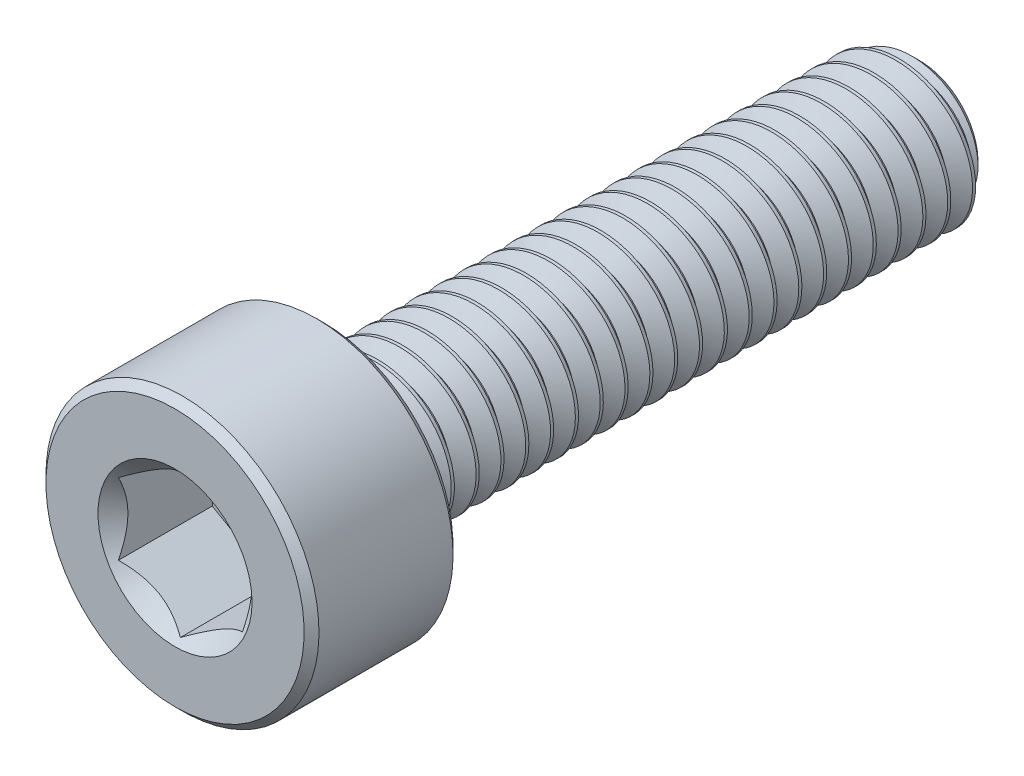
SolidWorks part; units mm, degrees
ref_plane "Front Plane" through (0, 0, 0) normal (0, 0, 1) x (1, 0, 0)
ref_plane "Top Plane" through (0, 0, 0) normal (0, 1, 0) x (1, 0, 0)
ref_plane "Right Plane" through (0, 0, 0) normal (1, 0, 0) x (0, 0, -1)
sketch "Sketch1" plane through (0, 0, 0) normal (1, 0, 0) x (0, 0, -1)
  line L0 (-7.5, 0) -> (7.5, 0) construction
  line L1 (7.5, 0) -> (7.5, 1.1752) construction
  line L2 (7.5, 1.1752) -> (7.1752, 1.5) construction
  line L3 (7.1752, 1.5) -> (7.125, 1.5) construction
  line L4 (7.125, 1.5) -> (-4.5, 1.5) construction
  line L5 (-4.5, 1.5) -> (-4.5, 2.75) construction
  line L6 (-4.5, 2.75) -> (-7.5, 2.75) construction
  line L7 (-7.5, 2.75) -> (-7.5, 0) construction
  line L8 (7.5, 1.1752) -> (7.5, 1.5) construction
  line L9 (7.4688, 1.5541) -> (7.7188, 1.1211) construction
  line L10 (7.7188, 1.1211) -> (7.9688, 1.5541) construction
  line L11 (7.9688, 1.5541) -> (7.4688, 1.5541) construction
  line L12 (7.7188, 1.5541) -> (7.7188, 1.5) construction
  line L13 (7.7188, 1.1211) -> (7.7188, 1.1752) construction
  line L14 (7.6875, 1.1752) -> (7.75, 1.1752) construction
  line L15 (7.5, 1.5) -> (7.9375, 1.5) construction
  line L16 (7.4844, 1.5271) -> (7.9531, 1.5271) construction
  line L17 (7.5, 0) -> (7.5, -1.5) construction
  line L18 (-4.65, 2.75) -> (-4.5, 2.6) construction
  line L19 (-7.35, 2.75) -> (-7.5, 2.6) construction
  line L20 (-4.5, 1.5) -> (-4.5, 0) construction
  line L21 (-4.5, 0.75) -> (-0.5, 0.75) construction
  line L22 (-0.5, 0.75) -> (3.5, 0.75) construction
  line L23 (3.5, 0.75) -> (7.5, 0.75) construction
  line L24 (-0.5, 0.75) -> (-0.5, 1.5) construction
  line L25 (-0.5, 1.5) -> (-0.5, 2.75) construction
  line L26 (3.5, 0.75) -> (3.5, 2.75) construction
  point P0 (-7.5, 1.25)
  point P3 (6.25, 1.5)
  point P4 (0, 0)
  point P18 (3.5, 1.5)
  point P22 (7.7188, 1.1752)
  point P24 (7.125, 1.5)
  point P25 (7.7188, 1.5)
  point P28 (7.7188, 1.5271)
  point P29 (6.25, -1.5)
  point P30 (-0.5, 1.5)
  point P31 (-6, 2.75)
  point P37 (-5.025, 2.75)
  point P38 (-7.275, 2.75)
  point P45 (-0.5, 0.75)
  point P46 (3.5, 0.75)
  dimension "D2" = 0.0625
  dimension "D7" = 0.15
  dimension "D8" = 0.15
  dimension "D9" = 0.15
  dimension "D10" = 0.075
  dimension "D11" = 0.375
  dimension "Drive Size" = 2.5
  dimension "Head Diameter" = 5.5
  dimension "Head Height" = 3
  dimension "Thread Pitch" = 0.5
  dimension "Thread Dia" = 3
  dimension "Length" = 12
  dimension "D12" = 0.375
  dimension "D4" = 1.25
  dimension "D3" = 45
sketch "Sketch2" plane through (0, 0, 0) normal (1, 0, 0) x (0, 0, -1)
  line L0 (-7.5, 0) -> (-7.5, 2.6)
  line L1 (-7.35, 2.75) -> (-4.65, 2.75)
  line L2 (-4.5, 2.6) -> (-4.5, 1.65)
  line L4 (7.1752, 1.5) -> (7.5, 1.1752)
  line L5 (7.5, 1.1752) -> (7.5, 0)
  line L6 (-4.5, 2.75) -> (-7.5, 2.75) construction
  line L7 (7.5, 0) -> (-7.5, 0)
  line L8 (-7.35, 2.75) -> (-7.5, 2.6) construction
  line L10 (-7.35, 2.75) -> (-7.5, 2.6)
  line L14 (-4.65, 2.75) -> (-4.5, 2.6) construction
  line L16 (-4.65, 2.75) -> (-4.5, 2.6)
  line L17 (-4.5, 1.5) -> (-4.5, 2.75) construction
  line L19 (-4.35, 1.5) -> (7.1752, 1.5)
  line L20 (7.125, 1.5) -> (-4.5, 1.5) construction
  arc A1 (-4.5, 1.65) -> (-4.35, 1.5) centre (-4.35, 1.65) ccw
  dimension "D3" = 0.15
revolve "Revolve1" add sketch "Sketch2" angle 360 about L7
sketch "Sketch3" plane through (0, 0, 7.5) normal (0, 0, 1) x (1, 0, 0)
  line L1 (1.25, -0.7217) -> (1.25, 0.7217)
  line L2 (1.25, 0.7217) -> (0, 1.4434)
  line L3 (0, 1.4434) -> (-1.25, 0.7217)
  line L4 (-1.25, 0.7217) -> (-1.25, -0.7217)
  line L5 (-1.25, -0.7217) -> (0, -1.4434)
  line L6 (0, -1.4434) -> (1.25, -0.7217)
  circle A0 centre (0, 0) radius 1.25 construction
  circle A1 centre (0, 0) radius 2.75 construction
  circle A2 centre (0, 0) radius 2.75 construction
  circle A3 centre (0, 0) radius 1.4434 construction
  point P13 (0, 0)
  dimension "D1" = 2.8868
extrude "Cut-Extrude1" cut sketch "Sketch3" against normal offset from surface (2 mm away) 1 up to face at (0, 2.6, 4.5)
sketch "Sketch4" plane through (0, 0, 7.5) normal (0, 0, 1) x (1, 0, 0)
  circle A0 centre (0, 0) radius 1.5516
  dimension "D1" = 3.1033
extrude "Cut-Extrude2" cut sketch "Sketch4" against normal up to vertex (1.5 mm away) draft 45 up to point (0, 2.75, 6)
sketch "Sketch11" plane through (0, 0, 0) normal (1, 0, 0) x (0, 0, -1)
  line L0 (-7.5, 0) -> (7.5, 0) construction
  line L1 (-7.5, 0) -> (7.5, 0) construction
  line L2 (-2.25, 0) -> (-2.25, 1.5) construction
  line L3 (7.125, 1.5) -> (-4.5, 1.5) construction
  line L4 (5.25, 0) -> (5.25, 1.5) construction
  line L6 (7.5, 1.1752) -> (7.5, 1.5) construction
  point P2 (-2.25, 0)
  point P3 (5.25, 0)
  dimension "D1" = 2.25
  dimension "D2" = 2.25
sketch "Sketch6" plane through (0, 0, -7.5) normal (0, 0, -1) x (-1, 0, 0)
  circle A0 centre (0, 0) radius 1.5
curve "Helix/Spiral1" pitch 0.5 height 12.5 radius 1.5 centre (0, 0, -7.5) axis (0, 0, 1) start towards (0, 1, 0)
sketch "Sketch10" plane through (0, 0, 0) normal (1, 0, 0) x (0, 0, -1)
  line L0 (-4.35, -2.75) -> (-4.35, 2.75)
  line L5 (-7.5, 0) -> (7.5, 0) construction
  line L6 (-4.35, 1.5) -> (-4.35, -1.5) construction
  point P3 (-4.35, 0)
split "Split1" trim tools "Sketch10" bodies to split 106 resulting bodies 114 115
sketch "Sketch7" plane through (0, 0, 0) normal (1, 0, 0) x (0, 0, -1)
  line L0 (7.4844, 1.5271) -> (7.9531, 1.5271)
  line L1 (7.9531, 1.5271) -> (7.75, 1.1752)
  line L2 (7.75, 1.1752) -> (7.6875, 1.1752)
  line L3 (7.6875, 1.1752) -> (7.4844, 1.5271)
sweep "Cut-Sweep1" cut profiles "Sketch7" path "Helix/Spiral1" align with end faces yes
sketch "Sketch8" plane through (0, 0, 0) normal (1, 0, 0) x (0, 0, -1)
  line L0 (-4.5, 0) -> (-4.5, 1.5)
  line L1 (-4.35, -1.5) -> (-4.35, 1.5) construction
  line L2 (-4.5, 1.5) -> (-4.35, 1.5)
  line L4 (-4.35, 1.5) -> (-3.484, 0)
  line L5 (-3.484, 0) -> (-4.5, 0)
  line L6 (7.125, 1.5) -> (-4.5, 1.5) construction
  line L7 (-7.5, 0) -> (7.5, 0) construction
  dimension "D1" = 60
revolve "Revolve2" add sketch "Sketch8" angle 360 about L5
equation "\"D2@Sketch1\" = \"Thread Pitch@Sketch1\" / 8"
equation "\"D4@Helix/Spiral1\" = \"Thread Pitch@Sketch1\""
equation "\"D7@Sketch1\" = \"Head Height@Sketch1\" * .05"
equation "\"D8@Sketch1\"=\"D7@Sketch1\""
equation "\"D9@Sketch1\"=\"D7@Sketch1\""
equation "\"D10@Sketch1\"=\"D7@Sketch1\"/2"
equation "\"D11@Sketch1\"=\"D10@Sketch1\"*5"
equation "\"D4@Sketch1\"=\"Thread Pitch@Sketch1\"*2.5"
equation "\"D12@Sketch1\"=\"Thread Pitch@Sketch1\"*.75"
equation "\"D3@Helix/Spiral1\"=\"Length@Sketch1\"+\"Thread Pitch@Sketch1\""
equation "\"D3@Sketch2\"=\"Thread Dia@Sketch1\"*0.05"
equation "\"D1@Sketch11\"=\"Length@Sketch1\"*0.1875"
equation "\"D2@Sketch11\"=\"D1@Sketch11\""
equation "\"D1@Sketch4\"=\"D1@Sketch3\"*1.075"
